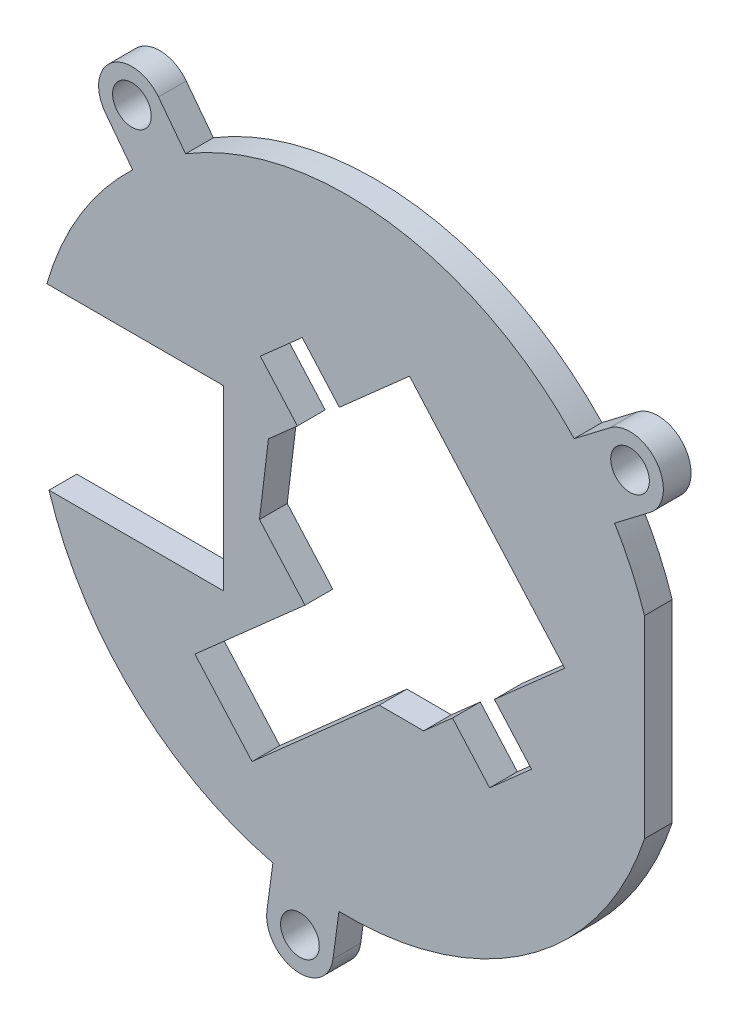
SolidWorks part; units mm, degrees
ref_plane "Front Plane" through (0, 0, 0) normal (0, 0, 1) x (1, 0, 0)
ref_plane "Top Plane" through (0, 0, 0) normal (0, 1, 0) x (1, 0, 0)
ref_plane "Right Plane" through (0, 0, 0) normal (1, 0, 0) x (0, 0, -1)
sketch "Sketch1" plane through (0, 0, 0) normal (0, 0, 1) x (1, 0, 0)
  line L0 (-21.141, 18.2245) -> (20.1141, 18.2245) construction
  line L1 (-4.8006, 1.8415) -> (-4.8006, -3.0861)
  line L2 (-4.8006, -3.0861) -> (-8.9662, -3.0861)
  line L3 (-8.9662, -3.0861) -> (-8.9662, -5.3514)
  line L4 (-8.9662, -5.3514) -> (-6.5786, -5.3514)
  line L5 (-4.9806, 7.3918) -> (-2.5835, 9.5123)
  line L6 (-2.5835, 9.5123) -> (-0.463, 7.1152)
  line L7 (-4.9806, 7.3918) -> (-2.8601, 4.9947)
  line L8 (3.2088, 10.3632) -> (-4.5153, 3.5306)
  line L9 (12.0777, 0.3371) -> (4.3536, -6.4955)
  line L10 (-4.5153, 3.5306) -> (-5.0276, -0.7207)
  line L11 (-5.0276, -0.7207) -> (0.0716, -6.4852)
  line L12 (0.0716, -6.4852) -> (4.3536, -6.4955)
  line L13 (-2.478, -3.6029) -> (7.6432, 5.3502) construction
  line L14 (3.2088, 10.3632) -> (12.0777, 0.3371)
  line L15 (3.2088, 10.3632) -> (11.8761, 18.0302)
  line L16 (-9.2588, -8.622) -> (-4.7522, -4.6355) construction
  line L17 (-9.2588, -8.622) -> (-5.994, -12.3128) construction
  line L18 (-4.7522, -4.6355) -> (-1.4874, -8.3263) construction
  line L19 (-5.994, -12.3128) -> (-1.4874, -8.3263) construction
  line L20 (12.0777, 0.3371) -> (20.228, 7.5468)
  line L21 (-6.5786, -5.3514) -> (-6.5786, -5.8039)
  line L22 (-6.5786, -5.8039) -> (-14.0208, -5.8039)
  line L23 (-14.0208, -5.8039) -> (-14.0208, 4.5593)
  line L24 (-14.0208, 4.5593) -> (-6.5786, 4.5593)
  line L25 (-6.5786, 4.5593) -> (-6.5786, 3.9924)
  line L26 (-6.5786, 3.9924) -> (-8.9662, 3.9924)
  line L27 (-8.9662, 3.9924) -> (-8.9662, 1.8415)
  line L28 (-8.9662, 1.8415) -> (-4.8006, 1.8415)
  line L29 (8.4059, -2.9109) -> (10.5264, -5.308)
  line L30 (10.5264, -5.308) -> (8.1292, -7.4285)
  line L31 (8.1292, -7.4285) -> (6.0088, -5.0313)
  line L32 (-4.7522, -4.6355) -> (-2.9639, -3.0536) construction
  line L33 (-1.4874, -8.3263) -> (0.5926, -6.4864) construction
  line L34 (-5.4555, -12.9216) -> (-0.9489, -8.9351)
  line L35 (-8.7203, -9.2308) -> (-4.2137, -5.2443)
  line L36 (-8.7203, -9.2308) -> (-5.4555, -12.9216)
  line L37 (-0.9489, -8.9351) -> (1.816, -6.4894)
  line L38 (-4.2137, -5.2443) -> (-2.4254, -3.6624)
  arc A0 (-15.2315, -0.5079) -> (3.302, 14.878) centre (0, 0) ccw construction
  circle A1 centre (0, 0) radius 21.59 construction
  circle A2 centre (0, 0) radius 21.59
  circle A3 centre (0, -18.415) radius 1.4224 construction
  circle A4 centre (0, 18.415) radius 1.4224 construction
  circle A5 centre (0, -18.415) radius 1.4224
  circle A6 centre (0, 18.415) radius 1.4224
  circle A7 centre (0, 0) radius 15.24
  dimension "D3" = 30.48
  dimension "D1" = 33.4645
  dimension "D2" = 20.0406
  dimension "D4" = 4.9276
  dimension "D5" = 2.7178
  dimension "D6" = 8.7122
  dimension "D7" = 7.8613
  dimension "D8" = 2.7178
  dimension "D9" = 3.2004
  dimension "D10" = 13.3858
  dimension "D11" = 3.1623
  dimension "D12" = 10.3124
  dimension "D13" = 8.6106
  dimension "D14" = 7.6962
  dimension "D15" = 6.0168
  dimension "D16" = 2.3876
  dimension "D17" = 4.9276
  dimension "D18" = 22.86
  dimension "D19" = 7.4422
  dimension "D20" = 5.0546
  dimension "D21" = 13.6652
  dimension "D22" = 29.2608
  dimension "D23" = 0.8128
extrude "Boss-Extrude1" add sketch "Sketch1" along normal blind 1.5875 contours L15 A7 L20 L9 L29 L30 L31 L12 L33 L19 L17 L16 L32 L11 L1 L2 L3 L4 L21 L22 L23 L24 L25 L26 L27 L28 L10 L8 L7 L5 L6 | L28 L27 L26 L25 L24 L23 L22 L21 L4 L3 L2 L1 L11 L10 | A7 L15 A2 L20 A6 A5 region at (-6.8834, 2.2726, 0) region at (-10.1343, -0.6067, 0) region at (-13.5004, -8.3055, 0)
sketch "Sketch2" plane through (0, 0, 1.5875) normal (0, 0, 1) x (1, 0, 0)
  line L0 (-5.0276, 2.3876) -> (-5.0276, -2.794)
  line L1 (-5.0276, 2.3876) -> (-10.4871, 2.3876)
  line L2 (-10.4871, 2.3876) -> (-10.4871, 3.8608)
  line L3 (-10.4871, 3.8608) -> (-7.085, 3.8608)
  line L4 (-7.085, 3.8608) -> (-7.085, 4.8768)
  line L5 (-7.085, 4.8768) -> (-14.4764, 4.8768)
  line L6 (-14.4764, 4.8768) -> (-14.4764, -5.2832)
  line L7 (-14.4764, -5.2832) -> (-7.085, -5.2832)
  line L8 (-7.085, -5.2832) -> (-7.085, -4.2672)
  line L9 (-7.085, -4.2672) -> (-10.4871, -4.2672)
  line L10 (-10.4871, -4.2672) -> (-10.4871, -2.794)
  line L11 (-10.4871, -2.794) -> (-5.0276, -2.794)
  line L12 (-5.0276, 2.3876) -> (-4.653, 2.3876)
  line L13 (-4.5153, 3.5306) -> (-5.0276, -0.7207) construction
  line L14 (-5.0276, -2.794) -> (-3.1935, -2.794)
  line L15 (-5.0276, -0.7207) -> (-2.4254, -3.6624) construction
  line L16 (-7.085, 3.8608) -> (-7.085, -4.2672)
  line L17 (-14.4764, 4.8768) -> (-21.032, 4.8768)
  line L18 (-14.4764, -5.2832) -> (-20.9336, -5.2832)
  arc A0 (11.8761, 18.0302) -> (20.228, 7.5468) centre (0, 0) ccw construction
  arc M2 (11.8761, 18.0302) -> (20.228, 7.5468) centre (0, 0) ccw
  dimension "D1" = 9.4488
  dimension "D2" = 7.3914
  dimension "D3" = 10.16
  dimension "D4" = 1.016
  dimension "D5" = 5.1816
  dimension "D6" = 5.4596
  dimension "D7" = 1.4732
  dimension "D8" = 1.143
extrude "Cut-Extrude3" cut sketch "Sketch2" against normal through all contours L10 L11 L0 L1 L2 L3 L4 L5 L6 L7 L8 L9 | L16 L3 L2 L1 | L16 L11 L10 L9 | L18 L6 L17 M2 region at (-11.0879, -0.2032, 1.5875) region at (-8.7861, 3.1242, 1.5875) region at (-8.7861, -3.5306, 1.5875) region at (-17.9346, -0.1913, 1.5875)
sketch "Sketch3" plane through (0, 0, 0) normal (0, 0, -1) x (-1, 0, 0)
  line L0 (-20.8712, -5.5245) -> (-16.9841, -5.5245)
  line L1 (-16.9841, -5.5245) -> (-20.8712, -5.5245) construction
  line L2 (-16.9841, -5.5245) -> (-16.9841, 4.6772)
  line L3 (-8.4059, -2.9109) -> (-20.228, 7.5468) construction
  line L4 (-16.9841, 5.5245) -> (-16.9841, -5.5245) construction
  line L5 (-16.9841, 4.6772) -> (-20.228, 7.5468)
  arc A0 (-20.228, 7.5468) -> (20.9336, -5.2832) centre (0, 0) ccw construction
  arc A1 (-20.228, 7.5468) -> (-20.8712, -5.5245) centre (0, 0) ccw
  arc A2 (-20.8712, -5.5245) -> (-20.8712, 5.5245) centre (0, 0) ccw construction
extrude "Cut-Extrude4" cut sketch "Sketch3" against normal through all
sketch "Sketch4" plane through (0, 0, 0) normal (0, 0, -1) x (-1, 0, 0)
  line L0 (-12.3201, -16.1591) -> (12.3201, 16.1591) construction
  line L1 (-13.8351, -15.0041) -> (10.8052, 17.3141)
  line L2 (-10.8052, -17.3141) -> (13.8351, 15.0041)
  line L3 (-16.1591, 12.3201) -> (16.1591, -12.3201) construction
  line L4 (-15.0041, 13.8351) -> (17.3141, -10.8052)
  line L5 (-17.3141, 10.8052) -> (15.0041, -13.8351)
  line L6 (-16.9841, 5.5245) -> (-16.9841, 4.6772)
  line L7 (-16.9841, 4.6772) -> (-12.4201, 0.64)
  line L8 (-8.4059, -2.9109) -> (-16.9841, 4.6772) construction
  line L9 (-12.4201, 0.64) -> (-3.5512, 10.6661)
  line L10 (0.463, 7.1152) -> (-11.8761, 18.0302) construction
  line L11 (-3.5512, 10.6661) -> (-8.9594, 15.4501)
  line L12 (5.0276, -0.7207) -> (2.4254, -3.6624) construction
  line L13 (0, 0) -> (2.7145, -20.1379) construction
  line L14 (1.8879, 0.2545) -> (4.6025, -19.8834)
  line L15 (-1.8879, -0.2545) -> (0.8266, -20.3924)
  line L16 (-16.1591, 12.3201) -> (12.3201, 16.1591) construction
  circle A0 centre (0, 0) radius 17.86
  arc A1 (-13.8351, -15.0041) -> (-10.8052, -17.3141) centre (-12.3201, -16.1591) ccw
  arc A2 (13.8351, 15.0041) -> (10.8052, 17.3141) centre (12.3201, 16.1591) ccw
  arc A3 (-15.0041, 13.8351) -> (-17.3141, 10.8052) centre (-16.1591, 12.3201) ccw
  arc A4 (15.0041, -13.8351) -> (17.3141, -10.8052) centre (16.1591, -12.3201) ccw
  circle A5 centre (12.3201, 16.1591) radius 1.1049
  circle A6 centre (16.1591, -12.3201) radius 1.1049
  circle A7 centre (-12.3201, -16.1591) radius 1.1049
  circle A8 centre (-16.1591, 12.3201) radius 1.1049
  arc A9 (1.8879, 0.2545) -> (-1.8879, -0.2545) centre (0, 0) ccw
  arc A10 (0.8266, -20.3924) -> (4.6025, -19.8834) centre (2.7145, -20.1379) ccw
  arc A11 (2.7145, -20.1379) -> (16.1591, -12.3201) centre (0, 0) ccw construction
  circle A12 centre (2.7145, -20.1379) radius 1.1049
  point P6 (0, 0)
  point P13 (0, 0)
  point P39 (1.3573, -10.0689)
  line M1 (-8.4059, -2.9109) -> (-16.9841, 4.6772)
  line M3 (-16.9841, -5.5245) -> (-20.8712, -5.5245)
  arc M4 (-20.8712, -5.5245) -> (20.9336, -5.2832) centre (0, 0) ccw
  line M5 (20.9336, -5.2832) -> (7.085, -5.2832)
  line M7 (7.085, 4.8768) -> (21.032, 4.8768)
  arc M8 (21.032, 4.8768) -> (-11.8761, 18.0302) centre (0, 0) ccw
  line M9 (-11.8761, 18.0302) -> (0.463, 7.1152)
  circle M24 centre (0, 18.415) radius 1.4224
  circle M25 centre (0, -18.415) radius 1.4224
  dimension "D1" = 3.81
  dimension "D2" = 3.81
  dimension "D3" = 13.97
extrude "Boss-Extrude2" add sketch "Sketch4" against normal up to vertex (1.5875 mm away) contours A0 L4 L9 M9 | L4 A0 L5 L9 | L5 A0 L6 L9 M1 | L4 A3 L5 A0 A8 | A2 L1 A0 L2 A5 M8 | A0 M24 | A0 M25 | A0 L15 M25 | L15 A0 M25 | A10 M4 | A2 M8 region at (13.4131, 4.8762, 0) region at (10.9588, 8.3691, 0) region at (16.2523, 10.0852, 0) region at (0.2829, -17.4804, 0) region at (-2.9174, -21.6425, 0) region at (8.1323, 11.4955, 0) region at (-0.7535, -17.5272, 0) region at (-0.9598, -18.5708, 0) region at (-10.0849, 16.2525, 0) region at (0, 17.4932, 0) region at (-13.2407, 17.3665, 0) up to point (10.5264, -5.308, 1.5875)
extrude "Cut-Extrude5" cut sketch "Sketch4<3>" against normal blind 2.54 contours A4 L5 A0 L2 A1 M25 M4 | A4 A0 L4 M4 M5 | A1 L1 A0 M3 M4 | A7 | A6 | A5 | A2 L2 A0 M7 M8 | A2 A0 L1 M8 M9 M24 | L1 A1 L2 A0 A7 M4 | A10 A4 L5 A0 L14 M4 | A4 L4 A0 L5 A6 M4 | A12 region at (16.6582, -10.306, 0) region at (13.002, -14.0284, 0) region at (5.4053, -18.8788, 0) region at (-9.8123, -16.8747, 0) region at (-5.4955, 17.2518, 0) region at (-15.6105, -14.0703, 0) region at (-16.798, 10.0037, 0) region at (-18.1332, -7.9591, 0) region at (-12.3201, 16.1591, 0) region at (-16.1591, -12.3201, 0) region at (12.3201, -16.1591, 0) region at (-2.7145, -20.1379, 0)
sketch "Sketch4<3>" plane through (0, 0, 0) normal (0, 0, -1) x (-1, 0, 0) same geometry as "Sketch4"
